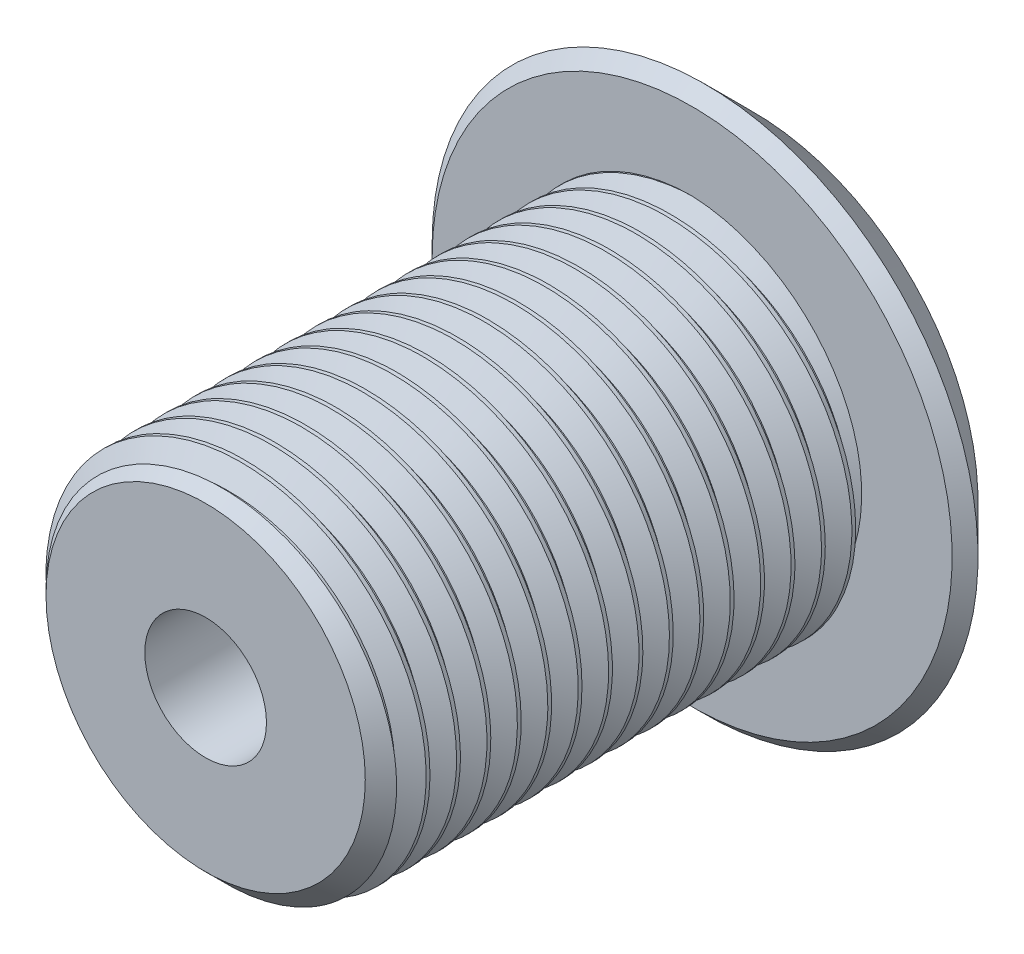
SolidWorks part; units mm, degrees
material "AISI 316 Annealed Stainless Steel Bar (SS)"
ref_plane "Front Plane" through (0, 0, 0) normal (0, 0, 1) x (1, 0, 0)
ref_plane "Top Plane" through (0, 0, 0) normal (0, 1, 0) x (1, 0, 0)
ref_plane "Right Plane" through (0, 0, 0) normal (1, 0, 0) x (0, 0, -1)
sketch "Sketch0" plane through (0, 0, 0) normal (1, 0, 0) x (0, 0, -1)
  line L0 (0, 0) -> (25.4, 0) construction
  point P2 (44.45, 0)
  point P4 (0, 0)
  dimension "D1" = 25.4
  dimension "D2" = 19.05
  dimension "Min Thread" = 0
sketch "Sketch1" plane through (0, 0, 0) normal (0, 0, 1) x (1, 0, 0)
  circle A0 centre (0, 0) radius 9.525
  dimension "OD" = 19.05
extrude "Extrude1" add sketch "Sketch1" against normal blind 25.4
sketch "Sketch2" plane through (0, 0, 0) normal (0, 0, 1) x (1, 0, 0)
  circle A0 centre (0, 0) radius 9.525 construction
  circle A1 centre (0, 0) radius 9.525
curve "Helix/Spiral1" pitch 1.5875 height 26.9875 turns 17 parameters "pitch"=1.5875
chamfer "Chamfer3" distance 1.1906 angle 45 1 edges at (9.525, 0, 0)
sketch "Sketch3" plane through (0, 0, 0) normal (1, 0, 0) x (0, 0, -1)
  line L0 (-1.3891, 9.525) -> (-0.7938, 8.4939)
  line L1 (-0.7938, 8.4939) -> (-0.5953, 8.4939)
  line L2 (-0.5953, 8.4939) -> (0, 9.525)
  line L3 (-1.3891, 9.525) -> (0, 9.525)
  line L4 (-0.6945, 9.525) -> (-0.6945, 8.4939) construction
  line L5 (-1.0914, 9.0094) -> (-0.2977, 9.0094) construction
  line L6 (0, 9.525) -> (0, -9.525) construction
  dimension "D1" = 0.1984
  dimension "D2" = 0.7937
  dimension "D3" = 60
sweep "Cut-Sweep1" cut profiles "Sketch3" path "Helix/Spiral1"
sketch "Sketch5" plane through (0, 0, 0) normal (1, 0, 0) x (0, 0, -1)
  line L0 (25.4, -8.5034) -> (25.4, 6.7963) construction
  line L1 (25.4, 9.525) -> (0, 9.525)
  line L2 (25.4, 9.525) -> (25.4, 0)
  line L3 (25.4, 0) -> (-3.4668, 0)
  line L4 (0, 0) -> (25.4, 0) construction
  line L5 (0, 9.525) -> (-3.4668, 0)
  line L6 (0, 0) -> (27.94, 0) construction
  dimension "D1" = 70
  dimension "D3" = 2.54
revolve "partially thread" [suppressed] add sketch "Sketch5" angle 360 about L6
sketch "Sketch6" plane through (0, 0, -25.4) normal (0, 0, -1) x (-1, 0, 0)
  circle A0 centre (0, 0) radius 14.2875
  dimension "head dia" = 28.575
extrude "Extrude2" add sketch "Sketch6" along normal blind 19.05
sketch "Sketch7" plane through (0, 0, -44.45) normal (0, 0, -1) x (-1, 0, 0)
  line L1 (0, 9.1654) -> (-7.9375, 4.5827)
  line L2 (-7.9375, 4.5827) -> (-7.9375, -4.5827)
  line L3 (-7.9375, -4.5827) -> (0, -9.1654)
  line L4 (0, -9.1654) -> (7.9375, -4.5827)
  line L5 (7.9375, -4.5827) -> (7.9375, 4.5827)
  line L6 (7.9375, 4.5827) -> (0, 9.1654)
  circle A0 centre (0, 0) radius 7.9375 construction
  dimension "hex dia" = 15.875
extrude "Cut-Extrude1" cut sketch "Sketch7" against normal blind 11.9062
sketch "Sketch8" plane through (0, 0, -44.45) normal (0, 0, -1) x (-1, 0, 0)
  circle A0 centre (0, 0) radius 9.1654
extrude "Cut-Extrude2" cut sketch "Sketch8" against normal through all draft 45
chamfer "Chamfer1" distance 1.4287 angle 45 1 edges at (-14.2875, 0, -44.45)
chamfer "Chamfer2" distance 0.7144 angle 45 1 edges at (-14.2875, 0, -25.4)
sketch "Sketch9" plane through (0, 0, 0) normal (1, 0, 0) x (0, 0, -1)
  line L0 (0, 9.525) -> (0, -9.525) construction
  line L1 (3.9687, 9.525) -> (3.9688, -9.525) construction
  line L2 (44.45, 14.2875) -> (44.45, -14.2875) construction
  line L3 (25.4, 14.2875) -> (25.4, -14.2875) construction
  line L4 (25.4, 13.5731) -> (25.4, -13.5731) construction
  line L5 (44.45, -12.8588) -> (44.45, 12.8588) construction
  line L6 (25.4, -14.2875) -> (25.4, 14.2875) construction
  line L7 (0, 8.3344) -> (0, -8.3344) construction
  line L8 (-1.3891, 9.525) -> (0, 9.525) construction
  line L9 (3.9688, 0) -> (0, 0) construction
  dimension "D1" = 3.9688
sketch "Sketch10" plane through (0, 0, -44.45) normal (0, 0, -1) x (-1, 0, 0)
  circle A0 centre (0, 0) radius 14.2875
  circle A1 centre (0, 0) radius 14.2875 construction
extrude "Cut-Extrude3" cut sketch "Sketch10" against normal offset from surface (15.875 mm away) 3.175
hole_wizard "1/4 (0.25) Diameter Hole1" positions "Sketch12" profile "Sketch13" hole size "1/4" standard "ANSI Inch" end condition through all
sketch "Sketch12" plane through (0, 0, -28.575) normal (0, 0, -1) x (-1, 0, 0)
  point P0 (0, 0)
sketch "Sketch13" plane through (0, 0, -28.575) normal (1, 0, 0) x (0, 1, 0)
  line L0 (0, 0) -> (0, 29.168)
  line L1 (0, 29.168) -> (3.175, 29.168)
  line L2 (3.175, 29.168) -> (3.175, 0)
  line L5 (3.175, 0) -> (0, 0)
  line L11 (0, -6.35) -> (0, 107.95) construction
  dimension "Thru Hole Dia." = 6.35
  dimension "Thru Hole Depth" = 29.168
chamfer "Chamfer4" distance 2.54 angle 45 1 edges at (-14.2875, 0, -28.575)
equation "\"D3@Helix/Spiral1\" = \"screw length@Extrude1\"+\"pitch@Helix/Spiral1\""
equation "\"D1@Sketch3\" = \"pitch@Helix/Spiral1\"*.125"
equation "\"D2@Sketch3\" = \"pitch@Helix/Spiral1\"*.5"
equation "\"D1@Cut-Extrude1\" = \"hex dia@Sketch7\"*.75"
equation "\"D1@Chamfer1\" = \"head dia@Sketch6\"*.05"
equation "\"D1@Sketch9\" = \"pitch@Helix/Spiral1\"*2.50"
equation "\"D1@Chamfer2\" = \"D1@Chamfer1\"/2"
equation "\"D1@Chamfer3\" = \"pitch@Helix/Spiral1\"*.750"
equation "\"D1@Sketch0\" = \"screw length@Extrude1\""
equation "\"D2@Sketch0\" = \"head depth@Extrude2\""
